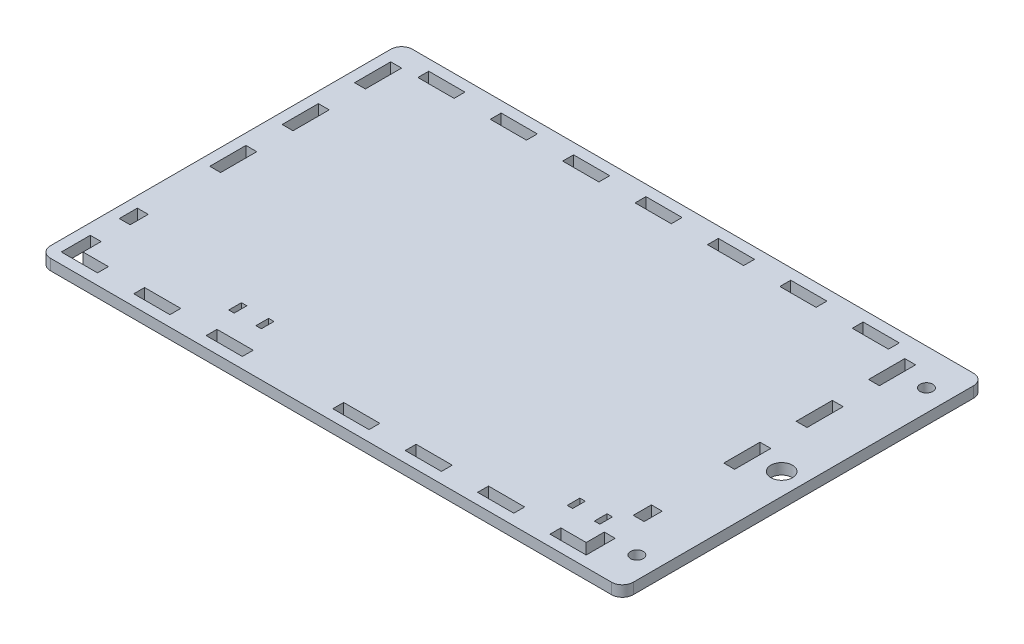
SolidWorks part; units mm, degrees
material "Maple"
ref_plane "Front Plane" through (0, 0, 0) normal (0, 0, 1) x (1, 0, 0)
ref_plane "Top Plane" through (0, 0, 0) normal (0, 1, 0) x (1, 0, 0)
ref_plane "Right Plane" through (0, 0, 0) normal (1, 0, 0) x (0, 0, -1)
sketch "Sketch1" plane through (0, 0, 0) normal (0, 1, 0) x (1, 0, 0)
  line L1 (0, 0) -> (151, 0)
  line L2 (0, 0) -> (0, -100)
  line L3 (0, -100) -> (151, -100)
  line L4 (151, 0) -> (151, -100)
  dimension "D1" = 151
  dimension "D2" = 100
extrude "Boss-Extrude1" add sketch "Sketch1" along normal blind 3
sketch "Sketch3" plane through (0, 0, 0) normal (0, -1, 0) x (1, 0, 0)
  line L0 (0, 86) -> (151, 86) construction
  line L1 (0, 100) -> (151, 100) construction
  line L2 (40, 87.75) -> (41.5, 87.75)
  line L3 (40, 87.75) -> (40, 84.25)
  line L4 (40, 84.25) -> (41.5, 84.25)
  line L5 (41.5, 87.75) -> (41.5, 84.25)
  line L6 (40, 87.75) -> (41.5, 84.25) construction
  line L7 (40, 84.25) -> (41.5, 87.75) construction
  line L8 (47.5, 87.75) -> (49, 87.75)
  line L9 (47.5, 87.75) -> (47.5, 84.25)
  line L10 (47.5, 84.25) -> (49, 84.25)
  line L11 (49, 87.75) -> (49, 84.25)
  line L12 (47.5, 87.75) -> (49, 84.25) construction
  line L13 (47.5, 84.25) -> (49, 87.75) construction
  line L14 (133.5, 87.75) -> (135, 87.75)
  line L15 (133.5, 87.75) -> (133.5, 84.25)
  line L16 (133.5, 84.25) -> (135, 84.25)
  line L17 (135, 87.75) -> (135, 84.25)
  line L18 (133.5, 87.75) -> (135, 84.25) construction
  line L19 (133.5, 84.25) -> (135, 87.75) construction
  line L20 (141, 87.75) -> (142.5, 87.75)
  line L21 (141, 87.75) -> (141, 84.25)
  line L22 (141, 84.25) -> (142.5, 84.25)
  line L23 (142.5, 87.75) -> (142.5, 84.25)
  line L24 (141, 87.75) -> (142.5, 84.25) construction
  line L25 (141, 84.25) -> (142.5, 87.75) construction
  line L26 (151, 100) -> (151, 0) construction
  line L27 (0, 0) -> (0, 100) construction
  point P2 (40.75, 86)
  point P7 (48.25, 86)
  point P12 (134.25, 86)
  point P17 (141.75, 86)
  dimension "D1" = 14
  dimension "D2" = 3.5
  dimension "D3" = 1.5
  dimension "D4" = 6
  dimension "D5" = 6
  dimension "D6" = 8.5
  dimension "D7" = 40
extrude "Cut-Extrude1" cut sketch "Sketch3" against normal through all
sketch "Sketch4" plane through (0, 0, 0) normal (0, -1, 0) x (1, 0, 0)
  line L0 (151, 100) -> (151, 0) construction
  line L1 (151, 100) -> (161, 100)
  line L2 (151, 100) -> (151, 0)
  line L3 (151, 0) -> (161, 0)
  line L4 (161, 100) -> (161, 0)
  line L5 (151, 0) -> (0, 0) construction
  dimension "D1" = 10
extrude "Boss-Extrude2" add sketch "Sketch4" against normal through all
sketch "Sketch5" plane through (0, 0, 0) normal (0, -1, 0) x (1, 0, 0)
  line L0 (161, 50) -> (0, 50) construction
  line L1 (161, 0) -> (161, 100) construction
  line L2 (0, 0) -> (0, 100) construction
  line L3 (155, 100) -> (155, 0) construction
  line L4 (0, 100) -> (161, 100) construction
  line L5 (161, 0) -> (0, 0) construction
  circle A0 centre (155, 50) radius 3
  circle A1 centre (155, 90) radius 1.75
  circle A2 centre (155, 10) radius 1.75
  dimension "D1" = 6
  dimension "D3" = 3.5
  dimension "D2" = 6
  dimension "D4" = 10
  dimension "D5" = 10
  dimension "D6" = 6
extrude "Cut-Extrude2" cut sketch "Sketch5" against normal through all
fillet "Fillet1" radius 3 2 edges at (0, 1.5, 0) (0, 1.5, 100)
fillet "Fillet2" radius 3 2 edges at (161, 1.5, 100) (161, 1.5, 0)
sketch "Sketch6" plane through (0, 3, 0) normal (0, 1, 0) x (1, 0, 0)
  line L2 (148, -94) -> (148, -89)
  line L3 (148, -89) -> (145, -89)
  line L4 (145, -94) -> (145, -89)
  line L5 (148, -81) -> (145, -81)
  line L6 (148, -81) -> (148, -76)
  line L7 (148, -76) -> (145, -76)
  line L8 (145, -81) -> (145, -76)
  line L9 (148, -56) -> (145, -56)
  line L10 (148, -56) -> (148, -46)
  line L11 (148, -46) -> (145, -46)
  line L12 (145, -56) -> (145, -46)
  line L13 (148, -36) -> (145, -36)
  line L14 (148, -36) -> (148, -26)
  line L15 (148, -26) -> (145, -26)
  line L16 (145, -36) -> (145, -26)
  line L17 (148, -16) -> (145, -16)
  line L18 (148, -16) -> (148, -6)
  line L19 (148, -6) -> (145, -6)
  line L20 (145, -16) -> (145, -6)
  line L21 (140.5, -6) -> (130.5, -6)
  line L22 (140.5, -6) -> (140.5, -3)
  line L23 (140.5, -3) -> (130.5, -3)
  line L24 (130.5, -6) -> (130.5, -3)
  line L25 (120.5, -6) -> (110.5, -6)
  line L26 (120.5, -6) -> (120.5, -3)
  line L27 (120.5, -3) -> (110.5, -3)
  line L28 (110.5, -6) -> (110.5, -3)
  line L29 (100.5, -6) -> (90.5, -6)
  line L30 (100.5, -6) -> (100.5, -3)
  line L31 (100.5, -3) -> (90.5, -3)
  line L32 (90.5, -6) -> (90.5, -3)
  line L33 (80.5, -6) -> (70.5, -6)
  line L34 (80.5, -6) -> (80.5, -3)
  line L35 (80.5, -3) -> (70.5, -3)
  line L36 (70.5, -6) -> (70.5, -3)
  line L37 (60.5, -6) -> (50.5, -6)
  line L38 (60.5, -6) -> (60.5, -3)
  line L39 (60.5, -3) -> (50.5, -3)
  line L40 (50.5, -6) -> (50.5, -3)
  line L41 (40.5, -6) -> (30.5, -6)
  line L42 (40.5, -6) -> (40.5, -3)
  line L43 (40.5, -3) -> (30.5, -3)
  line L44 (30.5, -6) -> (30.5, -3)
  line L45 (20.5, -6) -> (10.5, -6)
  line L46 (20.5, -6) -> (20.5, -3)
  line L47 (20.5, -3) -> (10.5, -3)
  line L48 (10.5, -6) -> (10.5, -3)
  line L49 (6, -16) -> (3, -16)
  line L50 (6, -16) -> (6, -6)
  line L51 (6, -6) -> (3, -6)
  line L52 (3, -16) -> (3, -6)
  line L53 (6, -36) -> (3, -36)
  line L54 (6, -36) -> (6, -26)
  line L55 (6, -26) -> (3, -26)
  line L56 (3, -36) -> (3, -26)
  line L57 (6, -56) -> (3, -56)
  line L58 (6, -56) -> (6, -46)
  line L59 (6, -46) -> (3, -46)
  line L60 (3, -56) -> (3, -46)
  line L61 (6, -81) -> (3, -81)
  line L62 (6, -81) -> (6, -76)
  line L63 (6, -76) -> (3, -76)
  line L64 (3, -81) -> (3, -76)
  line L66 (6, -94) -> (6, -89)
  line L67 (6, -89) -> (3, -89)
  line L68 (3, -94) -> (3, -89)
  line L97 (23, -94) -> (33, -94)
  line L98 (23, -94) -> (23, -97)
  line L99 (23, -97) -> (33, -97)
  line L100 (33, -94) -> (33, -97)
  line L101 (43, -94) -> (53, -94)
  line L102 (43, -94) -> (43, -97)
  line L103 (43, -97) -> (53, -97)
  line L104 (53, -94) -> (53, -97)
  line L109 (78, -94) -> (88, -94)
  line L110 (78, -94) -> (78, -97)
  line L111 (78, -97) -> (88, -97)
  line L112 (88, -94) -> (88, -97)
  line L113 (98, -94) -> (108, -94)
  line L114 (98, -94) -> (98, -97)
  line L115 (98, -97) -> (108, -97)
  line L116 (108, -94) -> (108, -97)
  line L117 (118, -94) -> (128, -94)
  line L118 (118, -94) -> (118, -97)
  line L119 (118, -97) -> (128, -97)
  line L120 (128, -94) -> (128, -97)
  line L121 (138, -94) -> (145, -94)
  line L122 (138, -94) -> (138, -97)
  line L123 (138, -97) -> (148, -97)
  line L124 (148, -94) -> (148, -97)
  line L125 (13, -94) -> (6, -94)
  line L126 (13, -94) -> (13, -97)
  line L127 (13, -97) -> (3, -97)
  line L128 (3, -94) -> (3, -97)
extrude "Cut-Extrude3" cut sketch "Sketch6" against normal through all
equation "\"D5@Sketch5\"=\"D4@Sketch5\""
